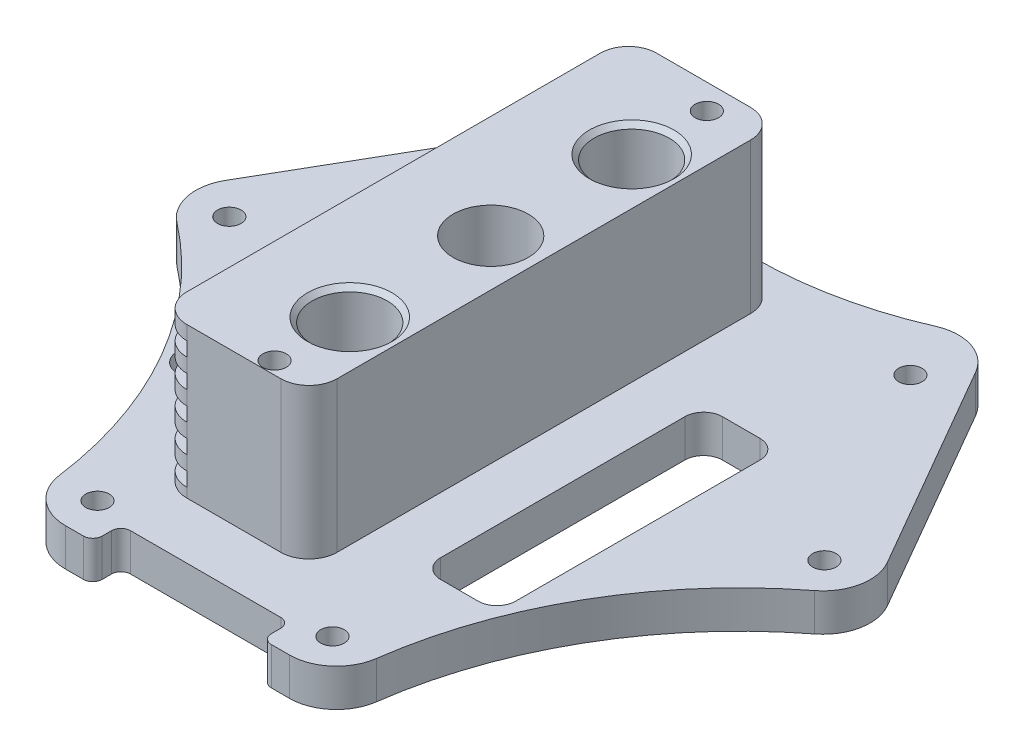
SolidWorks part; units mm, degrees
ref_plane "前基準面" through (0, 0, 0) normal (0, 0, 1) x (1, 0, 0)
ref_plane "上基準面" through (0, 0, 0) normal (0, 1, 0) x (1, 0, 0)
ref_plane "右基準面" through (0, 0, 0) normal (1, 0, 0) x (0, 0, -1)
sketch "草圖1" plane through (0, 0, 0) normal (0, 1, 0) x (1, 0, 0)
  line L0 (-20, 33.342) -> (20, 33.342) construction
  line L1 (20, 33.342) -> (37.5, 3.0311)
  line L2 (37.5, 3.0311) -> (16.5, -33.342) construction
  line L3 (16.5, -33.342) -> (-16.5, -33.342)
  line L4 (-16.5, -33.342) -> (-37.5, 3.0311) construction
  line L5 (-37.5, 3.0311) -> (-20, 33.342)
  line L6 (0, 33.342) -> (0, -33.342) construction
  arc A0 (-20, 33.342) -> (20, 33.342) centre (0, 67.983) ccw
  arc A1 (16.5, -33.342) -> (37.5, 3.0311) centre (61.4674, -35.0552) cw
  arc A2 (-37.5, 3.0311) -> (-16.5, -33.342) centre (-61.4674, -35.0552) cw
  dimension "D6" = 40
  dimension "D7" = 45
  dimension "D8" = 45
  dimension "D1" = 40
  dimension "D2" = 33
  dimension "D3" = 35
  dimension "D4" = 42
  dimension "D5" = 120
extrude "填料-伸長1" add sketch "草圖1" along normal blind 4
fillet "圓角1" radius 5 6 edges at (20, 2, -33.342) (-20, 2, -33.342) (-37.5, 2, -3.0311) (-16.5, 2, 33.342) (16.5, 2, 33.342) (37.5, 2, -3.0311)
sketch "草圖2" plane through (0, 4, 0) normal (0, 1, 0) x (1, 0, 0)
  line L0 (0, -17.0796) -> (0, 0) construction
  line L1 (-11, 25.658) -> (5, 25.658)
  line L2 (-11, 25.658) -> (-11, -24.342)
  line L3 (-11, -24.342) -> (5, -24.342)
  line L4 (5, 25.658) -> (5, -24.342)
  line L5 (-11.9201, -33.342) -> (11.9201, -33.342) construction
  dimension "D1" = 16
  dimension "D2" = 50
  dimension "D3" = 5
  dimension "D4" = 9
extrude "填料-伸長2" add sketch "草圖2" along normal blind 16
fillet "圓角2" radius 3 4 edges at (-11, 12, -25.658) (5, 12, -25.658) (5, 12, 24.342) (-11, 12, 24.342)
sketch "草圖3" plane through (0, 0, 24.342) normal (0, 0, 1) x (1, 0, 0)
  line L0 (-8, 20) -> (-8, 4) construction
  line L1 (-14.9251, 18.5) -> (-8, 18.5)
  line L2 (-14.9251, 18.5) -> (-14.9251, 17)
  line L3 (-14.9251, 17) -> (-8, 17)
  line L4 (-8, 18.5) -> (-8, 17)
  line L5 (-14.9251, 15.5) -> (-8, 15.5)
  line L6 (-14.9251, 15.5) -> (-14.9251, 14)
  line L7 (-14.9251, 14) -> (-8, 14)
  line L8 (-8, 15.5) -> (-8, 14)
  line L9 (-14.9251, 12.5) -> (-8, 12.5)
  line L10 (-14.9251, 12.5) -> (-14.9251, 11)
  line L11 (-14.9251, 11) -> (-8, 11)
  line L12 (-8, 12.5) -> (-8, 11)
  line L13 (-14.9251, 9.5) -> (-8, 9.5)
  line L14 (-14.9251, 9.5) -> (-14.9251, 8)
  line L15 (-14.9251, 8) -> (-8, 8)
  line L16 (-8, 9.5) -> (-8, 8)
  line L17 (-14.9251, 6.5) -> (-8, 6.5)
  line L18 (-14.9251, 6.5) -> (-14.9251, 5)
  line L19 (-14.9251, 5) -> (-8, 5)
  line L20 (-8, 6.5) -> (-8, 5)
  line L21 (-8, 20) -> (2, 20) construction
  dimension "D2" = 1.5
  dimension "D3" = 1.5
  dimension "D4" = 1.5
  dimension "D1" = 5
extrude "除料-伸長1" cut sketch "草圖3" against normal through all
sketch "草圖4" plane through (0, 4, 0) normal (0, 1, 0) x (1, 0, 0)
  line L0 (-11.9201, -33.342) -> (11.9201, -33.342) construction
  line L1 (11, 11.658) -> (19, 11.658)
  line L2 (11, 11.658) -> (11, -18.342)
  line L3 (11, -18.342) -> (19, -18.342)
  line L4 (19, 11.658) -> (19, -18.342)
  line L5 (5, -21.342) -> (5, 22.658) construction
  dimension "D1" = 30
  dimension "D2" = 15
  dimension "D3" = 6
  dimension "D4" = 8
extrude "除料-伸長2" cut sketch "草圖4" against normal through all
fillet "圓角3" radius 2 4 edges at (11, 2, 18.342) (11, 2, -11.658) (19, 2, -11.658) (19, 2, 18.342)
sketch "草圖5" plane through (0, 20, 0) normal (0, 1, 0) x (1, 0, 0)
  circle A0 centre (0, 0) radius 4
  dimension "D1" = 8
extrude "除料-伸長3" cut sketch "草圖5" against normal through all
sketch "草圖6" plane through (0, 4, 0) normal (0, 1, 0) x (1, 0, 0)
  line L0 (-11, -21.342) -> (-11, 22.658) construction
  line L1 (-22, 7.658) -> (-16, 7.658)
  line L2 (-22, 7.658) -> (-22, -13.342)
  line L3 (-22, -13.342) -> (-16, -13.342)
  line L4 (-16, 7.658) -> (-16, -13.342)
  line L5 (13, -18.342) -> (17, -18.342) construction
  point P4 (-11, 0.658)
  point P7 (15, -18.342)
  dimension "D1" = 6
  dimension "D2" = 5
  dimension "D3" = 5
  dimension "D4" = 21
extrude "除料-伸長4" cut sketch "草圖6" against normal through all
fillet "圓角4" radius 2 4 edges at (-22, 2, -7.658) (-16, 2, 13.342) (-16, 2, -7.658) (-22, 2, 13.342)
sketch "草圖7" plane through (0, 0, 0) normal (0, -1, 0) x (1, 0, 0)
  line L0 (0, 15) -> (0, -15) construction
  circle A0 centre (0, 15) radius 4
  circle A1 centre (0, -15) radius 4
  dimension "D1" = 8
  dimension "D2" = 8
  dimension "D3" = 15
extrude "除料-伸長5" cut sketch "草圖7" against normal through all
chamfer "導角1" distance 0.5 angle 45 2 edges at (0, 20, -19) (0, 20, 11)
hole_wizard "M10x1.0 螺紋孔1" positions "草圖9" profile "草圖8" tap size "M10x1.0" standard "Iso"
sketch "草圖9" plane through (0, 0, 0) normal (0, -1, 0) x (-1, 0, 0)
  point P0 (0, 15)
  point P3 (0, -15)
sketch "草圖8" plane through (0, 0, -15) normal (1, 0, 0) x (0, 0, -1)
  line L0 (0, 0) -> (0, 6.7039)
  line L1 (0, 6.7039) -> (4.5, 4)
  line L2 (4.5, 4) -> (4.5, 0)
  line L5 (4.5, 0) -> (0, 0)
  line L10 (0, 6.7039) -> (-4.5, 4) construction
  line L11 (0, -6.35) -> (0, 107.95) construction
  dimension "螺孔鑽直徑" = 9
  dimension "螺孔鑽深度" = 4
  dimension "導頭角度" = 118
cosmetic thread "鑽孔螺紋1" parameters "D1"=4, "D2"=10
cosmetic thread "鑽孔螺紋2" parameters "D1"=4, "D2"=10
sketch "草圖10" plane through (0, 0, 0) normal (0, -1, 0) x (1, 0, 0)
  line L0 (0, 23) -> (0, -23) construction
  circle A0 centre (0, 23) radius 1
  circle A1 centre (0, -23) radius 1
  dimension "D1" = 23
  dimension "D2" = 2
  dimension "D3" = 2
extrude "除料-伸長6" cut sketch "草圖10" against normal through all
hole_wizard "M3 螺紋孔1" positions "3D草圖1" profile "草圖11" tap size "M3" standard "Iso" end condition through all
sketch3d "3D草圖1"
  line L0 (0, 20, 23) -> (0, 0, 23) construction
  line L1 (0, 20, -23) -> (0, 0, -23) construction
  point P0 (0, 20, 23)
  point P4 (0, 20, -23)
sketch "草圖11" plane through (0, 20, 23) normal (1, 0, 0) x (0, 0, 1)
  line L0 (0, 0) -> (0, 20)
  line L1 (0, 20) -> (1.25, 20)
  line L2 (1.25, 20) -> (1.25, 0)
  line L5 (1.25, 0) -> (0, 0)
  line L11 (0, -6.35) -> (0, 107.95) construction
  dimension "貫穿螺孔鑽直徑" = 2.5
  dimension "貫穿螺孔鑽深度" = 20
cosmetic thread "鑽孔螺紋3" parameters "D2"=3
cosmetic thread "鑽孔螺紋4" parameters "D2"=3
sketch "草圖12" plane through (0, 4, 0) normal (0, 1, 0) x (1, 0, 0)
  line L0 (-16.9325, 22.6551) -> (-22.9325, 12.2628)
  line L1 (-22.9325, 12.2628) -> (-17.7363, 9.2628)
  line L2 (-17.7363, 9.2628) -> (-11.7363, 19.6551)
  line L3 (-11.7363, 19.6551) -> (-16.9325, 22.6551)
  line L4 (-22.3607, 29.2532) -> (-35.21, 6.9974) construction
  dimension "D1" = 8
  dimension "D2" = 6
  dimension "D3" = 12
  dimension "D4" = 3
extrude "除料-伸長7" cut sketch "草圖12" against normal through all
fillet "圓角5" radius 3 4 edges at (-11.7363, 2, -19.6551) (-17.7363, 2, -9.2628) (-22.9325, 2, -12.2628) (-16.9325, 2, -22.6551)
sketch "草圖17" plane through (0, 0, 0) normal (0, -1, 0) x (1, 0, 0)
  line L0 (-11.9201, 33.342) -> (11.9201, 33.342) construction
  line L1 (-9, 33.342) -> (9, 33.342)
  line L2 (-9, 33.342) -> (-9, 30.342)
  line L3 (-9, 30.342) -> (9, 30.342)
  line L4 (9, 33.342) -> (9, 30.342)
  line L5 (0, 0) -> (0, 30.342) construction
  dimension "D1" = 18
  dimension "D2" = 3
extrude "除料-伸長10" cut sketch "草圖17" against normal blind 4
sketch "草圖18" plane through (0, 4, 0) normal (0, 1, 0) x (1, 0, 0)
  line L0 (-12.5, -29.342) -> (12.5, -29.342) construction
  line L1 (0, 0) -> (0, -29.342) construction
  line L2 (9, -33.342) -> (11.9201, -33.342) construction
  circle A0 centre (-12.5, -29.342) radius 1
  circle A1 centre (12.5, -29.342) radius 1
  dimension "D3" = 2
  dimension "D4" = 2
  dimension "D1" = 25
  dimension "D2" = 4
extrude "除料-伸長11" cut sketch "草圖18" against normal through all
hole_wizard "M3 螺紋孔3" positions "3D草圖2" profile "草圖19" tap size "M3" standard "Iso" end condition through all
sketch3d "3D草圖2"
  line L0 (-12.5, 0, 29.342) -> (-12.5, 4, 29.342) construction
  line L1 (12.5, 0, 29.342) -> (12.5, 4, 29.342) construction
  point P0 (-12.5, 4, 29.342)
  point P4 (12.5, 4, 29.342)
sketch "草圖19" plane through (-12.5, 4, 29.342) normal (1, 0, 0) x (0, 0, 1)
  line L0 (0, 0) -> (0, 4)
  line L1 (0, 4) -> (1.25, 4)
  line L2 (1.25, 4) -> (1.25, 0)
  line L5 (1.25, 0) -> (0, 0)
  line L11 (0, -6.35) -> (0, 107.95) construction
  dimension "貫穿螺孔鑽直徑" = 2.5
  dimension "貫穿螺孔鑽深度" = 4
cosmetic thread "鑽孔螺紋7" parameters "D2"=3
cosmetic thread "鑽孔螺紋8" parameters "D2"=3
pattern_circular "環狀複製排列14" count 3 over 360 about axis through (0, 0, 0) along (0, 1, 0) of "除料-伸長11", "M3 螺紋孔3"
fillet "圓角8" radius 1 4 edges at (9, 2, 33.342) (9, 2, 30.342) (-9, 2, 33.342) (-9, 2, 30.342)
